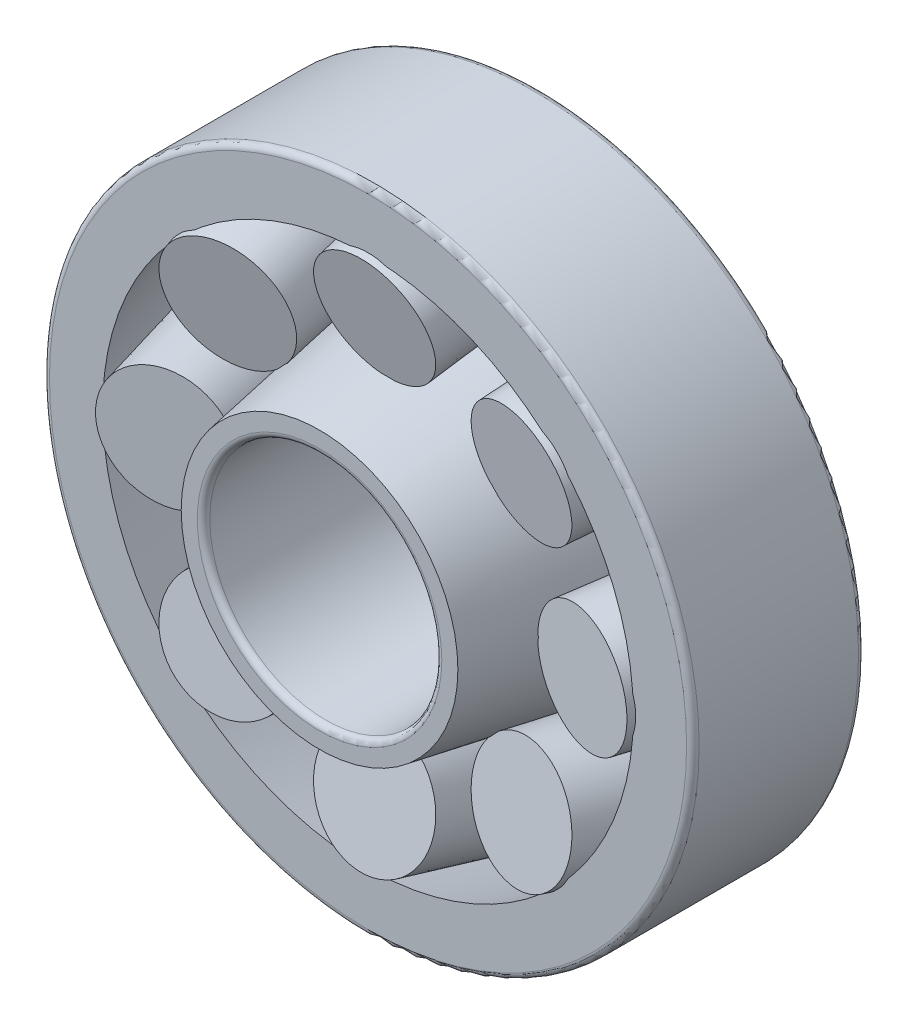
SolidWorks part; units mm, degrees
ref_plane "Front Plane" through (0, 0, 0) normal (0, 0, 1) x (1, 0, 0)
ref_plane "Top Plane" through (0, 0, 0) normal (0, 1, 0) x (1, 0, 0)
ref_plane "Right Plane" through (0, 0, 0) normal (1, 0, 0) x (0, 0, -1)
sketch "S" plane through (0, 0, 0) normal (0, 0, 1) x (1, 0, 0)
  line L0 (-7.125, 0) -> (7.125, 0) construction
  circle A0 centre (0, 0) radius 7.5 construction
  circle A1 centre (0, 0) radius 21 construction
  circle A2 centre (0, 0) radius 10.2 construction
  circle A3 centre (0, 0) radius 18.3 construction
  dimension "ID" = 15
  dimension "OD" = 42
  dimension "IDa" = 20.4
  dimension "ODa" = 36.6
  dimension "B" = 14.25
ref_axis "Z" through (0, 0, -7.8375) along (0, 0, 1)
sketch "ConeS" plane through (0, 0, 0) normal (0, 1, 0) x (1, 0, 0)
  line L0 (7.5, -7.125) -> (8.9437, -7.125)
  line L1 (8.9437, -7.125) -> (11.2051, 5.7)
  line L2 (11.2051, 5.7) -> (7.5, 5.7)
  line L3 (7.5, 5.7) -> (7.5, -7.125)
  line L4 (0, -11.6875) -> (0, 11.6875) construction
  dimension "x0" = 7.5
  dimension "y0" = 7.125
  dimension "x1" = 8.9437
  dimension "x2" = 11.2051
  dimension "y2" = 5.7
revolve "Cone" add sketch "ConeS" angle 360 about L4
sketch "CupS" plane through (0, 0, 0) normal (0, 1, 0) x (1, 0, 0)
  line L0 (17.1559, -3.99) -> (21, -3.99)
  line L1 (21, -3.99) -> (21, 7.125)
  line L2 (21, 7.125) -> (20.3431, 7.125)
  line L3 (20.3431, 7.125) -> (17.1559, -3.99)
  line L4 (0, -11.6875) -> (0, 11.6875) construction
  dimension "x0" = 17.1559
  dimension "y0" = 3.99
  dimension "x1" = 21
  dimension "y2" = 7.125
  dimension "x3" = 20.3431
revolve "Cup" add sketch "CupS" angle 360 about L4
sketch "RollerS" plane through (0, 0, 0) normal (0, 1, 0) x (1, 0, 0)
  line L0 (13.4252, -3.5625) -> (17.1792, -4.4317)
  line L1 (17.1792, -4.4317) -> (19.6187, 4.0118)
  line L2 (19.6187, 4.0118) -> (15.4048, 4.9875)
  line L3 (15.4048, 4.9875) -> (13.4252, -3.5625)
  dimension "x0" = 13.4252
  dimension "y0" = 3.5625
  dimension "x1" = 17.1792
  dimension "y1" = 4.4317
  dimension "x2" = 19.6187
  dimension "y2" = 4.0118
  dimension "x3" = 15.4048
  dimension "y3" = 4.9875
revolve "Roller" add sketch "RollerS" angle 360 about L3
pattern_circular "RollersPattern" count 8 over 360 about axis through (0, 0, -7.8375) along (0, 0, 1) of bodies 103
fillet "F1" radius 0.405 2 edges at (7.5, 0, -5.7) (7.5, 0, 7.125)
fillet "F2" radius 0.405 2 edges at (21, 0, -7.125) (21, 0, 3.99)
equation "\"x0@ConeS\" = abs(0.5*\"ID@S\")"
equation "\"y0@ConeS\" = abs(-0.5*\"B@S\")"
equation "\"x1@ConeS\" = abs(0.5*\"IDa@S\"-0.088163*\"B@S\")"
equation "\"x2@ConeS\" = abs(0.5*\"IDa@S\"+0.070531*\"B@S\")"
equation "\"y2@ConeS\" = abs(0.4*\"B@S\")"
equation "\"x0@CupS\" = abs(0.5*\"ODa@S\"-0.080289*\"B@S\")"
equation "\"y0@CupS\" = abs(-0.28*\"B@S\")"
equation "\"x1@CupS\" = abs(0.5*\"OD@S\")"
equation "\"y2@CupS\" = abs(0.5*\"B@S\")"
equation "\"x3@CupS\" = abs(0.5*\"ODa@S\"+0.143373*\"B@S\")"
equation "\"x0@RollerS\" = abs(0.25*\"IDa@S\"+0.25*\"ODa@S\"-0.057884*\"B@S\")"
equation "\"y0@RollerS\" = abs(-0.25*\"B@S\")"
equation "\"x1@RollerS\" = abs(0.006443*\"IDa@S\"+0.493557*\"ODa@S\"-0.071331*\"B@S\")"
equation "\"y1@RollerS\" = abs(-0.246887*\"B@S\"-0.056392*\"ODa@S\"+0.056392*\"IDa@S\")"
equation "\"x2@RollerS\" = abs(0.006443*\"IDa@S\"+0.493557*\"ODa@S\"+0.099863*\"B@S\")"
equation "\"y2@RollerS\" = abs(0.345641*\"B@S\"-0.056392*\"ODa@S\"+0.056392*\"IDa@S\")"
equation "\"x3@RollerS\" = abs(0.25*\"IDa@S\"+0.25*\"ODa@S\"+0.081038*\"B@S\")"
equation "\"y3@RollerS\" = abs(0.35*\"B@S\")"
equation "\"N@RollersPattern\" = int(4.833*(0.25*\"IDa@S\"+0.25*\"ODa@S\")/(0.5*\"ODa@S\"-0.5*\"IDa@S\"))"
equation "\"r_min@F2\" = \"r_min@F1\""
